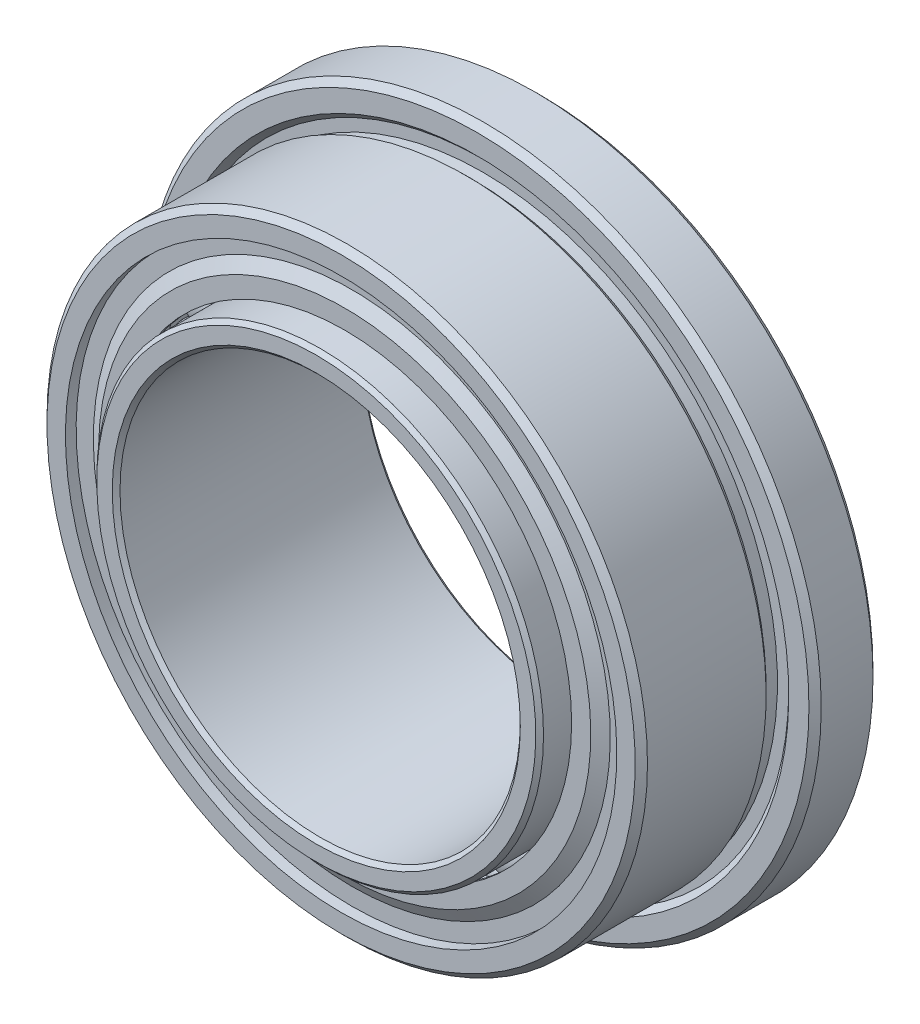
SolidWorks part; units mm, degrees
material "Alloy Steel"
ref_plane "Front Plane" through (0, 0, 0) normal (0, 0, 1) x (1, 0, 0)
ref_plane "Top Plane" through (0, 0, 0) normal (0, 1, 0) x (1, 0, 0)
ref_plane "Right Plane" through (0, 0, 0) normal (1, 0, 0) x (0, 0, -1)
sketch "Sketch1" plane through (0, 0, 0) normal (1, 0, 0) x (0, 0, -1)
  line L0 (0, 4.7625) -> (0, -4.7625) construction
  line L1 (-1.5875, 4.7625) -> (1.5875, 4.7625) construction
  line L2 (0, 0) -> (1.5875, 0) construction
  line L3 (1.5875, 5.3594) -> (1.5875, -5.3594) construction
  line L4 (1.5875, -5.3594) -> (0.5715, -5.3594) construction
  line L5 (1.5875, 3.175) -> (0, 3.175) construction
  line L6 (1.5875, 3.175) -> (1.5875, -3.175) construction
  line L7 (0, 3.5433) -> (0, -3.5433) construction
  line L8 (-1.9812, 3.5433) -> (1.9812, 3.5433) construction
  point P16 (0, 0)
  point P19 (0, 3.5433)
  dimension "OD" = 9.525
  dimension "Width" = 3.175
  dimension "Flange Dia." = 10.7188
  dimension "Flange Thickness" = 1.016
  dimension "ID" = 6.35
  dimension "Inner Ring OD" = 7.0866
  dimension "Inner Ring Width" = 3.9624
sketch "Sketch2" plane through (0, 0, 0) normal (1, 0, 0) x (0, 0, -1)
  line L0 (1.5875, 5.3594) -> (0.5715, 5.3594)
  line L1 (0.5715, 5.3594) -> (0.5715, 4.9421)
  line L2 (0.3919, 4.7625) -> (-1.5875, 4.7625)
  line L3 (-1.5875, 4.7625) -> (-1.5875, 4.1783)
  line L4 (-1.5875, 4.1783) -> (-0.2381, 4.1783)
  line L5 (1.5875, 5.3594) -> (1.5875, -5.3594) construction
  line L6 (1.5875, 4.1783) -> (1.5875, 5.3594)
  line L7 (1.9812, 3.175) -> (-1.9812, 3.175)
  line L8 (-1.9812, 3.175) -> (-1.9812, 3.5433)
  line L9 (-1.9812, 3.5433) -> (-0.2381, 3.5433)
  line L10 (1.9812, 3.5433) -> (1.9812, 3.175)
  line L11 (0, 4.7625) -> (0, 3.175) construction
  line L12 (-0.3969, 3.8608) -> (0.3969, 3.8608) construction
  line L13 (0.2381, 4.1783) -> (1.5875, 4.1783)
  line L14 (0.2381, 3.5433) -> (1.9812, 3.5433)
  line L15 (0.5715, 4.9421) -> (0.6613, 4.8523)
  line L16 (0.6613, 4.8523) -> (0.6613, 4.6727)
  line L17 (0.6613, 4.6727) -> (0.4817, 4.6727)
  line L18 (0.4817, 4.6727) -> (0.3919, 4.7625)
  line L19 (0.5715, 4.7625) -> (0.6613, 4.6727) construction
  line L20 (0.6613, 4.8523) -> (0.4817, 4.6727) construction
  line L21 (0.3919, 4.7625) -> (0.5715, 4.7625) construction
  line L22 (0.5715, 4.7625) -> (0.5715, 4.9421) construction
  line L23 (-1.5875, 4.1783) -> (-1.5875, 3.5433) construction
  line L24 (1.5875, 3.175) -> (0, 3.175) construction
  line L25 (-1.5875, 3.8608) -> (-0.3969, 3.8608) construction
  circle A0 centre (0, 3.8608) radius 0.3969 construction
  arc A1 (-0.2381, 4.1783) -> (0.2381, 4.1783) centre (0, 3.8608) cw
  arc A2 (-0.2381, 3.5433) -> (0.2381, 3.5433) centre (0, 3.8608) ccw
  dimension "D1" = 1.5875
  dimension "Ball Dia." = 0.7937
  dimension "D2" = 135
  dimension "D3" = 0.254
  dimension "D4" = 0.635
  dimension "Outer Ring Thickness" = 0.5842
  dimension "Inner Wall" = 0.3683
revolve "Revolve1" add sketch "Sketch2" angle 360 about L2
fillet "Fillet1" radius 0.0974 3 edges at (0, -5.3594, -1.5875) (0, -5.3594, -0.5715) (0, -4.7625, 1.5875) profile chamfer
sketch "Sketch3" plane through (0, 0, 0) normal (0, 0, 1) x (1, 0, 0)
  line L0 (-3.175, 0) -> (3.175, 0) construction
  line L1 (-4.7625, 0) -> (4.7625, 0) construction
  point P5 (0, 0)
  dimension "ID2" = 6.35
  dimension "OD2" = 9.525
fillet "Fillet2" radius 0.0614 4 edges at (0, -3.5433, -1.9812) (0, -3.175, -1.9812) (0, -3.5433, 1.9812) (0, -3.175, 1.9812) profile chamfer
sketch "Sketch7" plane through (0, 0, 0) normal (0, 0, 1) x (1, 0, 0)
  line L0 (0, 4.2577) -> (0, 3.4639)
  line L1 (0, 5.3594) -> (0, -5.3594) construction
  line L2 (-0.44, 4.2577) -> (0, 0) construction
  line L3 (0, 0) -> (0.44, 4.2577) construction
  line L4 (0.44, 4.2577) -> (-0.44, 4.2577) construction
  circle A0 centre (0, 3.8608) radius 0.3969 construction
  circle A1 centre (0, 0) radius 4.2577 construction
  circle A2 centre (0, 0) radius 3.4639 construction
  arc A4 (0, 4.2577) -> (0, 3.4639) centre (0, 3.8608) ccw
  dimension "D1" = 11.8
revolve "Revolve3" add sketch "Sketch7" angle 360 about L0
pattern_circular "CirPattern3" count 27 over 360 about axis through (0, 0, 0) along (0, 0, -1) of bodies 107
sketch "Sketch8" plane through (0, 0, 0) normal (1, 0, 0) x (0, 0, -1)
  line L1 (-1.5875, 4.1783) -> (-1.3607, 4.1783)
  line L2 (-1.5875, 4.1783) -> (-1.5875, 4.373)
  line L3 (-1.5875, 4.373) -> (-1.3607, 4.373)
  line L4 (-1.3607, 4.1783) -> (-1.3607, 4.373)
  line L5 (1.5875, 4.1783) -> (1.3607, 4.1783)
  line L6 (1.5875, 4.1783) -> (1.5875, 4.373)
  line L7 (1.5875, 4.373) -> (1.3607, 4.373)
  line L8 (1.3607, 4.1783) -> (1.3607, 4.373)
  dimension "D1" = 0.1947
  dimension "D2" = 0.2268
revolve "Cut-Revolve1" cut sketch "Sketch8" angle 360 about L2
sketch "Sketch9" plane through (0, 0, 0) normal (1, 0, 0) x (0, 0, -1)
  line L0 (-1.3607, 4.373) -> (-1.3607, 4.0847)
  line L1 (-1.3607, 4.0847) -> (-1.4741, 3.8883)
  line L2 (-1.4741, 3.8883) -> (-1.4741, 3.6)
  line L3 (1.4741, 3.6) -> (1.4741, 3.5433) construction
  line L4 (1.3607, 4.373) -> (1.3607, 4.0847)
  line L5 (1.3607, 4.0847) -> (1.4741, 3.8883)
  line L6 (1.4741, 3.8883) -> (1.4741, 3.6)
  line L8 (-1.4174, 4.373) -> (-1.4174, 4.0999)
  line L9 (-1.4174, 4.0999) -> (-1.5308, 3.9035)
  line L10 (-1.5308, 3.9035) -> (-1.5308, 3.6)
  line L11 (-1.3607, 4.373) -> (-1.4174, 4.373)
  line L12 (-1.4741, 3.6) -> (-1.5308, 3.6)
  line L13 (1.4174, 4.373) -> (1.4174, 4.0999)
  line L14 (1.4174, 4.0999) -> (1.5308, 3.9035)
  line L15 (1.5308, 3.9035) -> (1.5308, 3.6)
  line L16 (1.3607, 4.373) -> (1.4174, 4.373)
  line L17 (1.4741, 3.6) -> (1.5308, 3.6)
  line L18 (-1.3607, 4.0847) -> (-1.3607, 4.7019) construction
  line L19 (1.3607, 4.0847) -> (1.3607, 4.373) construction
  line L20 (-1.4741, 4.1783) -> (-1.4741, 3.5433) construction
  line L22 (-1.4741, 3.6) -> (-1.4741, 3.5433) construction
  line L23 (-1.3607, 4.1783) -> (-1.5875, 4.1783) construction
  line L24 (-1.9812, 3.5433) -> (1.9812, 3.5433) construction
  dimension "D2" = 150
  dimension "D1" = 150
  dimension "D3" = 0.0567
  dimension "D4" = 0.0567
  dimension "D5" = 0.2268
revolve "Revolve4" add sketch "Sketch9" angle 360 about L2
ref_axis "Center Axis 1" through (0, 0, -1.7463) along (0, 0, 1)
ref_plane "Contact Plane 1" through (0, 0, -0.5715) normal (0, 0, 1) x (1, 0, 0)
equation "\"D3@Sketch2\"=\"Flange Thickness@Sketch1\"/4"
equation "\"D1@Fillet1\"=\"Outer Ring Thickness@Sketch2\"/6"
equation "\"ID2@Sketch3\" = \"ID@Sketch1\""
equation "\"OD2@Sketch3\" = \"OD@Sketch1\""
equation "\"D1@Fillet2\"=\"Inner Wall@Sketch2\"/6"
equation "\"D4@Sketch2\"=\"D1@Sketch2\"*.4"
equation "\"Ball Dia.@Sketch2\"= \"D1@Sketch2\" * .5"
equation "\"D1@CirPattern3\"=360/\"D1@Sketch7\"-4"
equation "\"D1@Sketch8\"=\"Outer Ring Thickness@Sketch2\"/3"
equation "\"D2@Sketch8\"=\"D1@Sketch2\"/7"
equation "\"D3@Sketch9\"=\"D5@Sketch9\"/4"
equation "\"D4@Sketch9\"=\"D5@Sketch9\"/4"
equation "\"D1@Sketch9\"=\"D2@Sketch9\""
